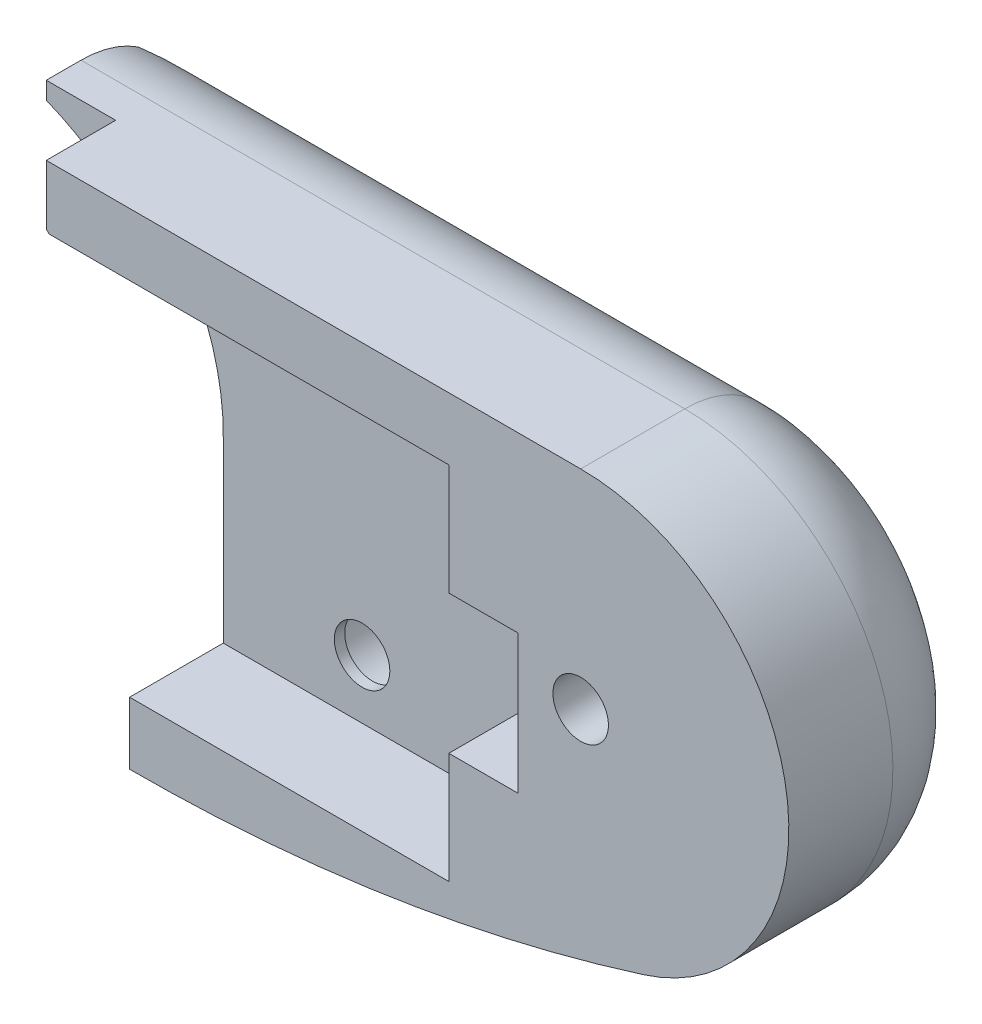
SolidWorks part; units mm, degrees
ref_plane "Front Plane" through (0, 0, 0) normal (0, 0, 1) x (1, 0, 0)
ref_plane "Top Plane" through (0, 0, 0) normal (0, 1, 0) x (1, 0, 0)
ref_plane "Right Plane" through (0, 0, 0) normal (1, 0, 0) x (0, 0, -1)
sketch "Sketch2" plane through (0, 0, 0) normal (0, 0, 1) x (1, 0, 0)
  line L0 (0.0004, -0.0013) -> (0.0004, 0.9987) construction
  line L1 (0.0004, 0.9987) -> (20.0004, 0.9987) construction
  line L2 (0.0004, 6.9987) -> (20.0004, 6.9987)
  line L3 (7, 0) -> (7, -7)
  line L5 (2.5981, 7) -> (2.5981, 6.4989)
  line L10 (0.0004, -7.0013) -> (0.0004, -0.0013) construction
  circle A0 centre (0.0004, -0.0013) radius 7
  circle A1 centre (20.0004, 0.9987) radius 6
  spline S0 degree 2 poles (21.8025, -4.7243) (14.5761, -6.9999) (7, -7) knots 0 0 0 1 1 1
extrude "Boss-Extrude1" add sketch "Sketch2" along normal blind 6 contours A1 A0 L3 | A1 region at (10.9508, 0.3536, 0) region at (20.0004, 0.9987, 0)
sketch "Sketch4" plane through (0, 0, 0) normal (0, 0, 1) x (1, 0, 0)
  line L0 (0, 5.2) -> (0, 0)
  line L1 (0, 0) -> (0, -5.2)
  line L2 (0, 5.2) -> (16.2, 5.2)
  line L3 (16.2, 5.2) -> (16.2, -5.2)
  line L4 (16.2, -5.2) -> (0, -5.2)
  line L5 (16.2, 0) -> (18.2, 0) construction
  line L6 (18.2, 0) -> (18.2, 2)
  line L7 (18.2, 2) -> (16.2, 2)
  line L8 (18.2, 0) -> (18.2, -2)
  line L9 (18.2, -2) -> (16.2, -2)
extrude "Middle Insert" cut sketch "Sketch4" along normal blind 2.7 from offset 3.3 contours L4 L3 L2 L0 L1 | L3 L5 L6 L7 | L5 L3 L9 L8 region at (8.1, 0, 0) region at (17.2, 1, 0) region at (17.2, -1, 0)
sketch "Sketch6" plane through (0, 0, 0) normal (0, 0, 1) x (1, 0, 0)
  line L1 (2.5981, 7) -> (4.5981, 7)
  line L2 (2.5981, 7) -> (2.5981, 5)
  line L3 (2.5981, 5) -> (4.5981, 5)
  line L4 (4.5981, 7) -> (4.5981, 5)
extrude "Middle Insert2" cut sketch "Sketch6" against normal blind 2 from offset 6
sketch "Sketch3" plane through (0, 0, 0) normal (0, 0, 1) x (1, 0, 0)
  line L0 (0, 0) -> (11, 0) construction
  line L1 (11, 0) -> (11, 1) construction
  line L2 (11, 0) -> (11, 3.5) construction
  line L3 (11, 0) -> (11, -3.5) construction
  line L5 (20.0004, 0.9987) -> (11, 1) construction
  circle A0 centre (20.0004, 0.9987) radius 0.8
  circle A1 centre (11, 3.5) radius 0.8
  circle A2 centre (11, -3.5) radius 0.8
extrude "Screw Holes" cut sketch "Sketch3" along normal through all
sketch "Sketch5" plane through (0, 0, 0) normal (0, 0, 1) x (1, 0, 0)
  circle A0 centre (20.0004, 0.9987) radius 1.25
  circle A1 centre (11, -3.5) radius 1.25
extrude "Screw Heads" cut sketch "Sketch5" along normal blind 3
fillet "Fillet1" radius 3 3 edges at (11.2992, 6.9987, 0) (25.9308, 1.9103, 0)
